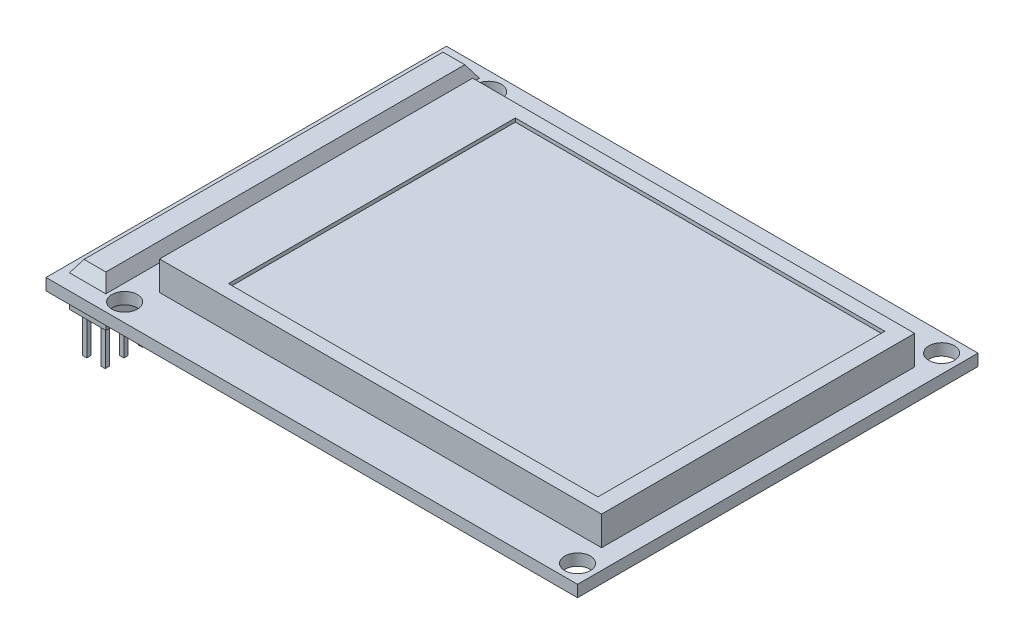
SolidWorks part; units mm, degrees
ref_plane "Front Plane" through (0, 0, 0) normal (0, 0, 1) x (1, 0, 0)
ref_plane "Top Plane" through (0, 0, 0) normal (0, 1, 0) x (1, 0, 0)
ref_plane "Right Plane" through (0, 0, 0) normal (1, 0, 0) x (0, 0, -1)
sketch "Sketch1" plane through (0, 0, 0) normal (0, 1, 0) x (1, 0, 0)
  line L1 (0, 0) -> (73, 0)
  line L2 (0, 0) -> (0, 55)
  line L3 (0, 55) -> (73, 55)
  line L4 (73, 0) -> (73, 55)
  dimension "D1" = 73
  dimension "D2" = 55
extrude "Boss-Extrude1" add sketch "Sketch1" along normal blind 1.6
sketch "Sketch2" plane through (0, 1.6, 0) normal (0, 1, 0) x (1, 0, 0)
  line L0 (73, 0) -> (73, 55) construction
  line L1 (9.6, 6) -> (70.3, 6)
  line L2 (9.6, 6) -> (9.6, 49)
  line L3 (9.6, 49) -> (70.3, 49)
  line L4 (70.3, 6) -> (70.3, 49)
  line L5 (0, 0) -> (73, 0) construction
  line L6 (73, 55) -> (0, 55) construction
  line L7 (0, 55) -> (0, 0) construction
  dimension "D1" = 2.7
  dimension "D2" = 6
  dimension "D3" = 6
  dimension "D4" = 9.6
extrude "Boss-Extrude2" add sketch "Sketch2" along normal blind 4
sketch "Sketch3" plane through (0, 0, 0) normal (0, -1, 0) x (1, 0, 0)
  line L0 (0, 0) -> (73, 0) construction
  line L1 (0, -55) -> (7, -55) construction
  line L2 (0, -55) -> (0, 0) construction
  line L3 (0, 0) -> (7, 0) construction
  line L4 (7, -55) -> (7, 0) construction
  line L5 (2.23, -55) -> (2.23, 0) construction
  line L6 (4.77, 0) -> (4.77, -55) construction
  line L7 (4.77, -52.069) -> (2.23, -52.069) construction
  line L8 (6.06, -2.16) -> (1.06, -2.16)
  line L9 (6.06, -2.16) -> (6.06, -53.46)
  line L10 (6.06, -53.46) -> (1.06, -53.46)
  line L11 (1.06, -2.16) -> (1.06, -53.46)
  line L12 (5.095, -52.394) -> (4.445, -52.394) construction
  line L13 (5.095, -52.394) -> (5.095, -51.744) construction
  line L14 (5.095, -51.744) -> (4.445, -51.744) construction
  line L15 (4.445, -52.394) -> (4.445, -51.744) construction
  line L16 (5.095, -52.394) -> (4.445, -51.744) construction
  line L17 (5.095, -51.744) -> (4.445, -52.394) construction
  line L18 (1.905, -52.394) -> (2.555, -52.394) construction
  line L19 (1.905, -52.394) -> (1.905, -51.744) construction
  line L20 (1.905, -51.744) -> (2.555, -51.744) construction
  line L21 (2.555, -52.394) -> (2.555, -51.744) construction
  line L22 (1.905, -52.394) -> (2.555, -51.744) construction
  line L23 (1.905, -51.744) -> (2.555, -52.394) construction
  point P15 (4.77, -52.069)
  point P20 (2.23, -52.069)
  dimension "D2" = 2.54
  dimension "D3" = 2.23
  dimension "D4" = 51.3
  dimension "D5" = 2.16
  dimension "D6" = 1.06
  dimension "D7" = 5
  dimension "D8" = 0.65
extrude "Boss-Extrude3" add sketch "Sketch3" along normal blind 2.75
sketch "Sketch4" plane through (0, -2.75, 0) normal (0, -1, 0) x (1, 0, 0)
  line L0 (2.23, -55) -> (2.23, 0) construction
  line L2 (4.77, 0) -> (4.77, -55) construction
  line L3 (7, -55) -> (7, 0) construction
  line L4 (2.53, -26.53) -> (1.93, -26.53)
  line L5 (2.53, -26.53) -> (2.53, -25.93)
  line L6 (2.53, -25.93) -> (1.93, -25.93)
  line L7 (1.93, -26.53) -> (1.93, -25.93)
  line L8 (2.53, -26.53) -> (1.93, -25.93) construction
  line L9 (2.53, -25.93) -> (1.93, -26.53) construction
  line L10 (0, -55) -> (0, 0) construction
  line L11 (2.23, -55) -> (2.23, 0) construction
  line L12 (4.77, 0) -> (4.77, -55) construction
  line L13 (7, -55) -> (7, 0) construction
  line L14 (0, -55) -> (0, 0) construction
  line L15 (7, -27.5) -> (0, -27.5) construction
  line L16 (7, -26.23) -> (0, -26.23) construction
  line L17 (6.3052, -26.23) -> (6.3052, -28.77) construction
  line L18 (7, -28.77) -> (0, -28.77) construction
  line L19 (2.53, -25.93) -> (4.47, -25.93) construction
  line L20 (4.47, -25.93) -> (5.07, -25.93)
  line L21 (5.07, -25.93) -> (5.07, -26.53)
  line L22 (5.07, -26.53) -> (4.47, -26.53)
  line L23 (4.47, -26.53) -> (4.47, -25.93)
  line L24 (4.47, -25.93) -> (5.07, -26.53) construction
  line L25 (5.07, -25.93) -> (4.47, -26.53) construction
  line L26 (2.53, -23.99) -> (1.93, -23.99)
  line L27 (1.93, -23.99) -> (1.93, -23.39)
  line L28 (2.53, -23.39) -> (1.93, -23.39)
  line L29 (2.53, -23.99) -> (2.53, -23.39)
  line L30 (4.47, -23.99) -> (4.47, -23.39)
  line L31 (4.47, -23.39) -> (5.07, -23.39)
  line L32 (5.07, -23.39) -> (5.07, -23.99)
  line L33 (5.07, -23.99) -> (4.47, -23.99)
  line L34 (2.53, -21.45) -> (1.93, -21.45)
  line L35 (1.93, -21.45) -> (1.93, -20.85)
  line L36 (2.53, -20.85) -> (1.93, -20.85)
  line L37 (2.53, -21.45) -> (2.53, -20.85)
  line L38 (4.47, -21.45) -> (4.47, -20.85)
  line L39 (4.47, -20.85) -> (5.07, -20.85)
  line L40 (5.07, -20.85) -> (5.07, -21.45)
  line L41 (5.07, -21.45) -> (4.47, -21.45)
  line L42 (2.53, -18.91) -> (1.93, -18.91)
  line L43 (1.93, -18.91) -> (1.93, -18.31)
  line L44 (2.53, -18.31) -> (1.93, -18.31)
  line L45 (2.53, -18.91) -> (2.53, -18.31)
  line L46 (4.47, -18.91) -> (4.47, -18.31)
  line L47 (4.47, -18.31) -> (5.07, -18.31)
  line L48 (5.07, -18.31) -> (5.07, -18.91)
  line L49 (5.07, -18.91) -> (4.47, -18.91)
  line L50 (2.53, -16.37) -> (1.93, -16.37)
  line L51 (1.93, -16.37) -> (1.93, -15.77)
  line L52 (2.53, -15.77) -> (1.93, -15.77)
  line L53 (2.53, -16.37) -> (2.53, -15.77)
  line L54 (4.47, -16.37) -> (4.47, -15.77)
  line L55 (4.47, -15.77) -> (5.07, -15.77)
  line L56 (5.07, -15.77) -> (5.07, -16.37)
  line L57 (5.07, -16.37) -> (4.47, -16.37)
  line L58 (2.53, -13.83) -> (1.93, -13.83)
  line L59 (1.93, -13.83) -> (1.93, -13.23)
  line L60 (2.53, -13.23) -> (1.93, -13.23)
  line L61 (2.53, -13.83) -> (2.53, -13.23)
  line L62 (4.47, -13.83) -> (4.47, -13.23)
  line L63 (4.47, -13.23) -> (5.07, -13.23)
  line L64 (5.07, -13.23) -> (5.07, -13.83)
  line L65 (5.07, -13.83) -> (4.47, -13.83)
  line L66 (2.53, -11.29) -> (1.93, -11.29)
  line L67 (1.93, -11.29) -> (1.93, -10.69)
  line L68 (2.53, -10.69) -> (1.93, -10.69)
  line L69 (2.53, -11.29) -> (2.53, -10.69)
  line L70 (4.47, -11.29) -> (4.47, -10.69)
  line L71 (4.47, -10.69) -> (5.07, -10.69)
  line L72 (5.07, -10.69) -> (5.07, -11.29)
  line L73 (5.07, -11.29) -> (4.47, -11.29)
  line L74 (2.53, -8.75) -> (1.93, -8.75)
  line L75 (1.93, -8.75) -> (1.93, -8.15)
  line L76 (2.53, -8.15) -> (1.93, -8.15)
  line L77 (2.53, -8.75) -> (2.53, -8.15)
  line L78 (4.47, -8.75) -> (4.47, -8.15)
  line L79 (4.47, -8.15) -> (5.07, -8.15)
  line L80 (5.07, -8.15) -> (5.07, -8.75)
  line L81 (5.07, -8.75) -> (4.47, -8.75)
  line L82 (2.53, -6.21) -> (1.93, -6.21)
  line L83 (1.93, -6.21) -> (1.93, -5.61)
  line L84 (2.53, -5.61) -> (1.93, -5.61)
  line L85 (2.53, -6.21) -> (2.53, -5.61)
  line L86 (4.47, -6.21) -> (4.47, -5.61)
  line L87 (4.47, -5.61) -> (5.07, -5.61)
  line L88 (5.07, -5.61) -> (5.07, -6.21)
  line L89 (5.07, -6.21) -> (4.47, -6.21)
  line L90 (2.53, -3.67) -> (1.93, -3.67)
  line L91 (1.93, -3.67) -> (1.93, -3.07)
  line L92 (2.53, -3.07) -> (1.93, -3.07)
  line L93 (2.53, -3.67) -> (2.53, -3.07)
  line L94 (4.47, -3.67) -> (4.47, -3.07)
  line L95 (4.47, -3.07) -> (5.07, -3.07)
  line L96 (5.07, -3.07) -> (5.07, -3.67)
  line L97 (5.07, -3.67) -> (4.47, -3.67)
  line L98 (5.07, -29.07) -> (4.47, -28.47) construction
  line L99 (4.47, -29.07) -> (5.07, -28.47) construction
  line L100 (2.53, -29.07) -> (4.47, -29.07) construction
  line L101 (2.53, -29.07) -> (1.93, -28.47) construction
  line L102 (2.53, -28.47) -> (1.93, -29.07) construction
  line L103 (5.07, -51.33) -> (4.47, -51.33)
  line L104 (5.07, -51.93) -> (5.07, -51.33)
  line L105 (4.47, -51.93) -> (5.07, -51.93)
  line L106 (4.47, -51.33) -> (4.47, -51.93)
  line L107 (2.53, -51.33) -> (2.53, -51.93)
  line L108 (2.53, -51.93) -> (1.93, -51.93)
  line L109 (1.93, -51.33) -> (1.93, -51.93)
  line L110 (2.53, -51.33) -> (1.93, -51.33)
  line L111 (5.07, -48.79) -> (4.47, -48.79)
  line L112 (5.07, -49.39) -> (5.07, -48.79)
  line L113 (4.47, -49.39) -> (5.07, -49.39)
  line L114 (4.47, -48.79) -> (4.47, -49.39)
  line L115 (2.53, -48.79) -> (2.53, -49.39)
  line L116 (2.53, -49.39) -> (1.93, -49.39)
  line L117 (1.93, -48.79) -> (1.93, -49.39)
  line L118 (2.53, -48.79) -> (1.93, -48.79)
  line L119 (5.07, -46.25) -> (4.47, -46.25)
  line L120 (5.07, -46.85) -> (5.07, -46.25)
  line L121 (4.47, -46.85) -> (5.07, -46.85)
  line L122 (4.47, -46.25) -> (4.47, -46.85)
  line L123 (2.53, -46.25) -> (2.53, -46.85)
  line L124 (2.53, -46.85) -> (1.93, -46.85)
  line L125 (1.93, -46.25) -> (1.93, -46.85)
  line L126 (2.53, -46.25) -> (1.93, -46.25)
  line L127 (5.07, -43.71) -> (4.47, -43.71)
  line L128 (5.07, -44.31) -> (5.07, -43.71)
  line L129 (4.47, -44.31) -> (5.07, -44.31)
  line L130 (4.47, -43.71) -> (4.47, -44.31)
  line L131 (2.53, -43.71) -> (2.53, -44.31)
  line L132 (2.53, -44.31) -> (1.93, -44.31)
  line L133 (1.93, -43.71) -> (1.93, -44.31)
  line L134 (2.53, -43.71) -> (1.93, -43.71)
  line L135 (5.07, -41.17) -> (4.47, -41.17)
  line L136 (5.07, -41.77) -> (5.07, -41.17)
  line L137 (4.47, -41.77) -> (5.07, -41.77)
  line L138 (4.47, -41.17) -> (4.47, -41.77)
  line L139 (2.53, -41.17) -> (2.53, -41.77)
  line L140 (2.53, -41.77) -> (1.93, -41.77)
  line L141 (1.93, -41.17) -> (1.93, -41.77)
  line L142 (2.53, -41.17) -> (1.93, -41.17)
  line L143 (5.07, -38.63) -> (4.47, -38.63)
  line L144 (5.07, -39.23) -> (5.07, -38.63)
  line L145 (4.47, -39.23) -> (5.07, -39.23)
  line L146 (4.47, -38.63) -> (4.47, -39.23)
  line L147 (2.53, -38.63) -> (2.53, -39.23)
  line L148 (2.53, -39.23) -> (1.93, -39.23)
  line L149 (1.93, -38.63) -> (1.93, -39.23)
  line L150 (2.53, -38.63) -> (1.93, -38.63)
  line L151 (5.07, -36.09) -> (4.47, -36.09)
  line L152 (5.07, -36.69) -> (5.07, -36.09)
  line L153 (4.47, -36.69) -> (5.07, -36.69)
  line L154 (4.47, -36.09) -> (4.47, -36.69)
  line L155 (2.53, -36.09) -> (2.53, -36.69)
  line L156 (2.53, -36.69) -> (1.93, -36.69)
  line L157 (1.93, -36.09) -> (1.93, -36.69)
  line L158 (2.53, -36.09) -> (1.93, -36.09)
  line L159 (5.07, -33.55) -> (4.47, -33.55)
  line L160 (5.07, -34.15) -> (5.07, -33.55)
  line L161 (4.47, -34.15) -> (5.07, -34.15)
  line L162 (4.47, -33.55) -> (4.47, -34.15)
  line L163 (2.53, -33.55) -> (2.53, -34.15)
  line L164 (2.53, -34.15) -> (1.93, -34.15)
  line L165 (1.93, -33.55) -> (1.93, -34.15)
  line L166 (2.53, -33.55) -> (1.93, -33.55)
  line L167 (5.07, -31.01) -> (4.47, -31.01)
  line L168 (5.07, -31.61) -> (5.07, -31.01)
  line L169 (4.47, -31.61) -> (5.07, -31.61)
  line L170 (4.47, -31.01) -> (4.47, -31.61)
  line L171 (2.53, -31.01) -> (2.53, -31.61)
  line L172 (2.53, -31.61) -> (1.93, -31.61)
  line L173 (1.93, -31.01) -> (1.93, -31.61)
  line L174 (2.53, -31.01) -> (1.93, -31.01)
  line L175 (5.07, -28.47) -> (4.47, -28.47)
  line L176 (5.07, -29.07) -> (5.07, -28.47)
  line L177 (4.47, -29.07) -> (5.07, -29.07)
  line L178 (4.47, -28.47) -> (4.47, -29.07)
  line L179 (2.53, -28.47) -> (2.53, -29.07)
  line L180 (2.53, -29.07) -> (1.93, -29.07)
  line L181 (1.93, -28.47) -> (1.93, -29.07)
  line L182 (2.53, -28.47) -> (1.93, -28.47)
  point P21 (2.23, -26.23)
  point P22 (4.77, -26.23)
  point P28 (6.3052, -27.5)
  point P179 (4.77, -28.77)
  point P180 (2.23, -28.77)
  dimension "D1" = 0.6
  dimension "D2" = 2.54
  dimension "D3" = 10
extrude "Boss-Extrude4" add sketch "Sketch4" along normal blind 5.5
sketch "Sketch5" plane through (0, 0, 0) normal (0, -1, 0) x (1, 0, 0)
  line L0 (73, 0) -> (73, -55) construction
  line L1 (66.5, -13) -> (50, -13)
  line L2 (66.5, -13) -> (66.5, -42)
  line L3 (66.5, -42) -> (50, -42)
  line L4 (50, -13) -> (50, -42)
  line L7 (73, -55) -> (0, -55) construction
  line L8 (0, 0) -> (73, 0) construction
  dimension "D1" = 13
  dimension "D2" = 13
  dimension "D3" = 23
  dimension "D4" = 6.5
extrude "Boss-Extrude5" add sketch "Sketch5" along normal blind 3
sketch "Sketch10" plane through (0, 1.6, 0) normal (0, 1, 0) x (1, 0, 0)
  line L0 (70.5, 52.5) -> (8.3, 52.5) construction
  line L1 (8.3, 52.5) -> (8.3, 2.5) construction
  line L2 (8.3, 2.5) -> (70.5, 2.5) construction
  line L3 (70.5, 2.5) -> (70.5, 52.5) construction
  line L4 (73, 55) -> (0, 55) construction
  line L5 (73, 0) -> (73, 55) construction
  line L6 (0, 55) -> (0, 0) construction
  line L7 (0, 0) -> (73, 0) construction
  circle A0 centre (70.5, 52.5) radius 1.75
  circle A1 centre (70.5, 2.5) radius 1.75
  circle A2 centre (8.3, 2.5) radius 1.75
  circle A3 centre (8.3, 52.5) radius 1.75
  dimension "D1" = 3.5
  dimension "D2" = 2.5
  dimension "D3" = 2.5
  dimension "D4" = 8.3
  dimension "D5" = 2.5
extrude "Cut-Extrude3" cut sketch "Sketch10" against normal through all
sketch "Sketch6" plane through (73, 0, 0) normal (1, 0, 0) x (0, 0, -1)
  line L3 (13.05, 0) -> (41.95, 0)
  line L6 (41.95, 0) -> (41.95, -2.95)
  line L7 (41.95, -2.95) -> (13.05, -2.95)
  line L8 (13.05, -2.95) -> (13.05, 0)
  line L9 (41.95, 0) -> (41.95, -2.95)
  line L10 (41.95, -2.95) -> (13.05, -2.95)
  line L11 (13.05, -2.95) -> (13.05, 0)
  dimension "D1" = 0.05
extrude "Cut-Extrude1" cut sketch "Sketch6" against normal blind 30
sketch "Sketch7" plane through (0, 1.6, 0) normal (0, 1, 0) x (1, 0, 0)
  line L4 (6.06, 2.16) -> (6.06, 53.46)
  line L5 (6.06, 2.16) -> (6.06, 53.46)
  line L6 (1.06, 2.16) -> (6.06, 2.16)
  line L7 (1.06, 2.16) -> (6.06, 2.16)
  line L8 (1.06, 53.46) -> (1.06, 2.16)
  line L9 (1.06, 53.46) -> (1.06, 2.16)
  line L10 (6.06, 53.46) -> (1.06, 53.46)
  line L11 (6.06, 53.46) -> (1.06, 53.46)
  dimension "D1" = 0
extrude "Boss-Extrude6" add sketch "Sketch7" along normal blind 1.6 draft 32
sketch "Sketch8" plane through (0, 0, 0) normal (0, -1, 0) x (1, 0, 0)
  line L0 (73, -55) -> (0, -55) construction
  line L1 (45, -40) -> (34, -40)
  line L2 (45, -40) -> (45, -14)
  line L3 (45, -14) -> (34, -14)
  line L4 (34, -40) -> (34, -14)
  line L5 (73, 0) -> (73, -55) construction
  line L6 (73, 0) -> (73, -55) construction
  line L7 (0, 0) -> (73, 0) construction
  line L8 (73, -55) -> (0, -55) construction
  line L9 (22, -44) -> (15, -44)
  line L10 (22, -44) -> (22, -36)
  line L11 (22, -36) -> (15, -36)
  line L12 (15, -44) -> (15, -36)
  dimension "D1" = 15
  dimension "D2" = 39
  dimension "D3" = 28
  dimension "D4" = 14
  dimension "D5" = 51
  dimension "D6" = 11
  dimension "D7" = 58
  dimension "D8" = 19
extrude "Boss-Extrude7" add sketch "Sketch8" along normal blind 1.6 draft 15
sketch "Sketch9" plane through (0, 5.6, 0) normal (0, 1, 0) x (1, 0, 0)
  line L1 (17.26, 47.2) -> (68, 47.2)
  line L2 (17.26, 47.2) -> (17.26, 7.8)
  line L3 (17.26, 7.8) -> (68, 7.8)
  line L4 (68, 47.2) -> (68, 7.8)
  line L7 (73, 55) -> (0, 55) construction
  line L8 (0, 0) -> (73, 0) construction
  line L9 (0, 55) -> (0, 0) construction
  line L10 (73, 0) -> (73, 55) construction
  dimension "D1" = 7.8
  dimension "D2" = 7.8
  dimension "D3" = 39.4
  dimension "D4" = 17.26
  dimension "D5" = 5
extrude "Cut-Extrude2" cut sketch "Sketch9" against normal blind 0.5
